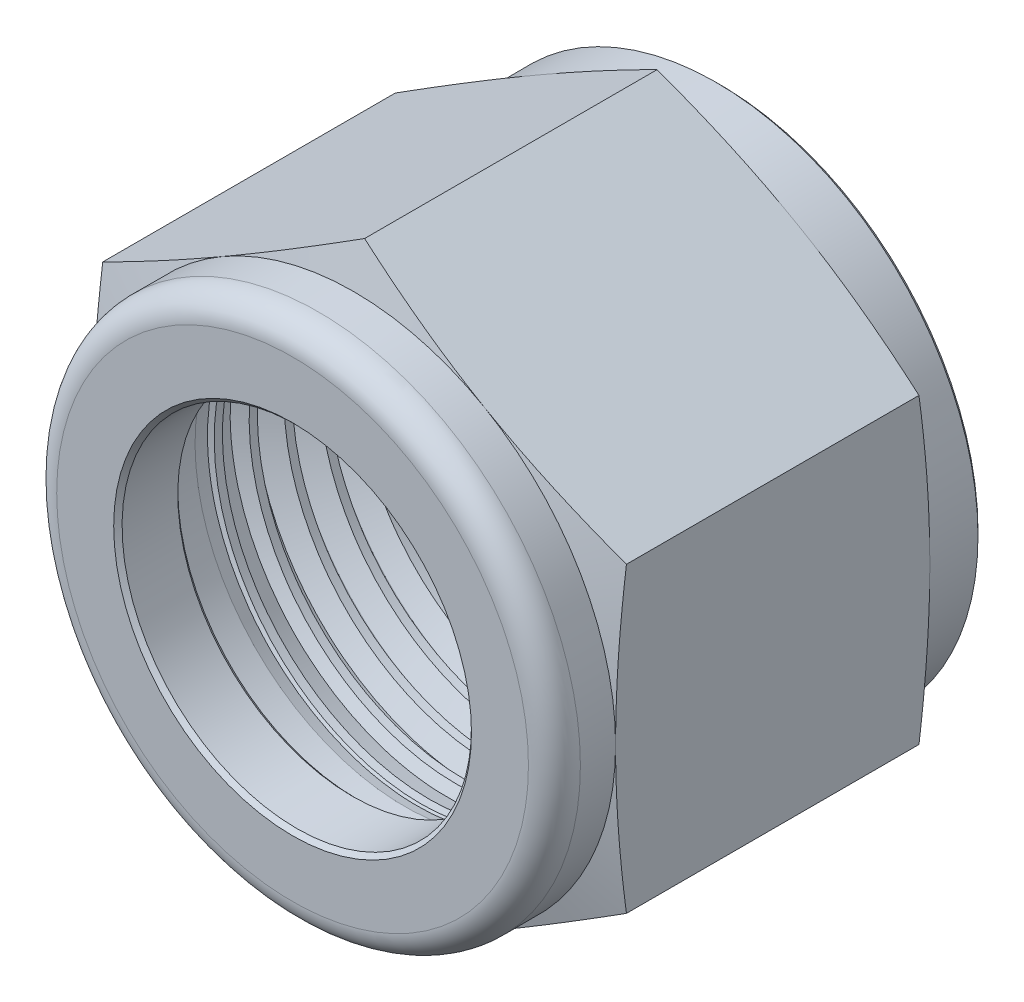
SolidWorks part; units mm, degrees
ref_plane "Front Plane" through (0, 0, 0) normal (0, 0, 1) x (1, 0, 0)
ref_plane "Top Plane" through (0, 0, 0) normal (0, 1, 0) x (1, 0, 0)
ref_plane "Right Plane" through (0, 0, 0) normal (1, 0, 0) x (0, 0, -1)
sketch "Sketch0" plane through (0, 0, 0) normal (1, 0, 0) x (0, 0, -1)
  line L0 (0, 0) -> (-25.9334, 0) construction
  line L4 (-25.9334, 15.875) -> (-25.9334, -15.875) construction
  line L5 (-25.9334, 15.875) -> (-25.9334, -15.875) construction
  line L6 (-25.9334, 10.5918) -> (-25.9334, -10.5918) construction
  line L7 (0, 13.4937) -> (0, -13.4937) construction
  line L8 (0, -13.4874) -> (0, 13.4874) construction
  line L9 (0, -13.4874) -> (-2.1167, -13.4874) construction
  point P16 (-22.0472, 0)
  point P20 (-19.1262, 0)
  point P22 (-13.6398, 0)
  point P34 (-3.175, 0)
  point P35 (-22.225, 0)
  dimension "P" = 31.75
  dimension "M" = 25.9334
  dimension "L" = 22.0472
  dimension "S" = 19.1262
  dimension "Q" = 13.6398
  dimension "A" = 21.1836
  dimension "C" = 31.75
  dimension "T" = 26.9875
  dimension "B" = 3.175
  dimension "J" = 19.05
  dimension "H" = 26.9748
  dimension "Pitch" = 2.1167
sketch "Sketch1" plane through (0, 0, 0) normal (0, 0, 1) x (1, 0, 0)
  line L1 (0, 18.3309) -> (-15.875, 9.1654)
  line L2 (-15.875, 9.1654) -> (-15.875, -9.1654)
  line L3 (-15.875, -9.1654) -> (0, -18.3309)
  line L4 (0, -18.3309) -> (15.875, -9.1654)
  line L5 (15.875, -9.1654) -> (15.875, 9.1654)
  line L6 (15.875, 9.1654) -> (0, 18.3309)
  circle A0 centre (0, 0) radius 15.875 construction
extrude "Boss-Extrude1" add sketch "Sketch1" along normal up to vertex (25.9334 mm away) up to point (0, 0, 25.9334)
sketch "Sketch2" plane through (0, 0, 0) normal (1, 0, 0) x (0, 0, -1)
  line L0 (-25.9334, 20.7867) -> (-25.9334, 15.875)
  line L1 (-25.9334, 15.875) -> (-22.225, 15.875)
  line L2 (-22.225, 15.875) -> (-21.567, 18.3309)
  line L3 (-25.9334, 18.3309) -> (0, 18.3309) construction
  line L4 (-21.567, 18.3309) -> (-3.833, 18.3309)
  line L5 (-3.833, 18.3309) -> (-3.175, 15.875)
  line L6 (-3.175, 15.875) -> (-22.225, 15.875) construction
  line L7 (-3.175, 15.875) -> (0, 15.875)
  line L8 (0, 15.875) -> (0, 20.7867)
  line L9 (-25.9334, 20.7867) -> (0, 20.7867)
  line L10 (-3.175, 15.875) -> (-3.175, 0) construction
  line L11 (-22.225, 15.875) -> (-22.225, 0) construction
  line L12 (-25.9334, 10.5918) -> (-25.9334, 0)
  line L13 (-25.9334, 15.875) -> (-25.9334, -15.875) construction
  line L14 (-25.9334, 0) -> (0, 0)
  line L15 (0, 0) -> (0, 12.7204)
  line L16 (-22.0472, 10.5918) -> (-22.0472, 0) construction
  line L17 (-22.0472, 10.5918) -> (-22.0472, 12.4664)
  line L18 (-21.7932, 12.7204) -> (0, 12.7204)
  line L19 (-22.0472, 10.5918) -> (-25.9334, 10.5918)
  line L23 (-19.1262, 0) -> (-19.1262, 12.7204) construction
  arc A0 (-22.0472, 12.4664) -> (-21.7932, 12.7204) centre (-21.7932, 12.4664) cw
  dimension "D3" = 0.254
  dimension "D1" = 15
  dimension "D2" = 15
  dimension "D4" = 0.7733
revolve "Cut-Revolve1" cut sketch "Sketch2" angle 360 about L0
sketch "Sketch3" plane through (0, 0, 0) normal (0, 0, -1) x (-1, 0, 0)
  circle A0 centre (0, 0) radius 12.7204
  circle A1 centre (0, 0) radius 12.7204 construction
  point P3 (0, 12.7204)
fillet "Fillet1" radius 1.5748 1 edges at (15.875, 0, 25.9334)
chamfer "Chamfer1" distance 0.254 angle 45 1 edges at (15.875, 0, 0)
chamfer "Chamfer2" distance 0.254 angle 45 2 edges at (0, 10.5918, 22.0472) (0, 10.5918, 25.9334)
ref_axis "Centre Axis 1" through (0, 0, 25.2505) along (0, 0, -1)
curve "Helix/Spiral1" pitch 2.1167 height 21.2429 radius 12.7204 centre (0, 0, 0) axis (0, 0, 1) start towards (0, 1, 0) parameters "Pitch"=2.1167
sketch "Sketch4" plane through (0, 0, 0) normal (1, 0, 0) x (0, 0, -1)
  line L0 (-0.248, 12.2908) -> (1.8686, 12.2908) construction
  line L1 (1.8686, 12.2908) -> (0.8103, 14.1239) construction
  line L2 (0.8103, 14.1239) -> (-0.248, 12.2908) construction
  line L3 (0.7111, 13.952) -> (0.9095, 13.952) construction
  line L4 (0.8103, 12.7204) -> (0.8103, 12.2908) construction
  line L5 (0, 12.7204) -> (1.6206, 12.7204) construction
  line L6 (0.8103, 14.1239) -> (0.8103, 13.952) construction
  line L7 (0.7111, 13.952) -> (-0.124, 12.5056)
  line L8 (-0.124, 12.5056) -> (1.7446, 12.5056)
  line L9 (1.7446, 12.5056) -> (0.9095, 13.952)
  arc A0 (0.9095, 13.952) -> (0.7111, 13.952) centre (0.8103, 13.8947) ccw
  point P6 (0.8103, 12.5056)
  dimension "D1" = 2.1167
  dimension "D2" = 1.8331
  dimension "D4" = 0.4296
  dimension "D3" = 0.1719
  dimension "D5" = 1.2316
sweep "Cut-Sweep1" cut profiles "Sketch4" path "Helix/Spiral1" align with end faces yes
sketch "Sketch5" plane through (0, 0, 0) normal (0, 0, -1) x (-1, 0, 0)
  circle A0 centre (0, 0) radius 13.4874
extrude "Cut-Extrude1" cut sketch "Sketch5" against normal through all draft 45
sketch "Sketch6" plane through (0, 0, 0) normal (1, 0, 0) x (0, 0, -1)
  line L0 (-22.0472, 14.1239) -> (-13.6398, 14.1239)
  line L1 (-13.6398, 14.1239) -> (-19.1262, 12.7204)
  line L2 (-19.1262, 12.7204) -> (-22.0472, 12.7204)
  line L3 (-22.0472, 12.7204) -> (-22.0472, 14.1239)
  line L4 (-13.6398, 0) -> (-13.6398, 14.1239) construction
  line L5 (-19.1262, 0) -> (-19.1262, 12.7204) construction
  line L7 (-22.0472, 12.7204) -> (-22.0472, 0) construction
  line L8 (-21.7932, 12.7204) -> (0, 12.7204) construction
  line L9 (-13.6398, 14.1239) -> (0.8103, 14.1239) construction
revolve "Revolve1" add sketch "Sketch6" angle 360 about L0
sketch "SketchX" plane through (0, 0, 0) normal (0, 0, -1) x (-1, 0, 0)
  line L0 (0, 0) -> (-6.7437, 11.6804) construction
  line L1 (-7.9375, 13.7482) -> (-15.875, 9.1654) construction
  circle A0 centre (0, 0) radius 13.4874 construction
equation "\"D3@Helix/Spiral1\"= \"Pitch@Sketch0\" + \"S@Sketch0\""
equation "\"D1@Sketch4\"=\"Pitch@Sketch0\""
equation "\"Pitch@Helix/Spiral1\"=\"Pitch@Sketch0\""
